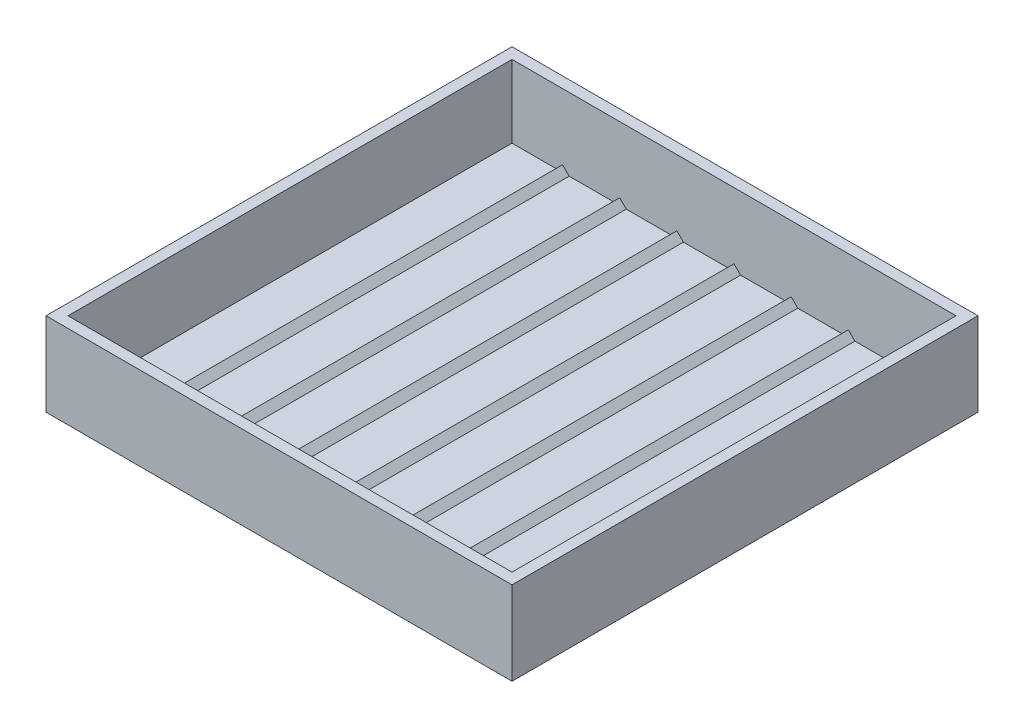
SolidWorks part; units mm, degrees
ref_plane "Front Plane" through (0, 0, 0) normal (0, 0, 1) x (1, 0, 0)
ref_plane "Top Plane" through (0, 0, 0) normal (0, 1, 0) x (1, 0, 0)
ref_plane "Right Plane" through (0, 0, 0) normal (1, 0, 0) x (0, 0, -1)
sketch "Sketch1" plane through (0, 0, 0) normal (0, 0, 1) x (1, 0, 0)
  line L0 (-50.5, -7) -> (-40.5, -7)
  line L1 (53, -9.5) -> (-53, -9.5)
  line L2 (53, -9.5) -> (53, 9.5)
  line L3 (53, 9.5) -> (-53, 9.5)
  line L4 (-53, -9.5) -> (-53, 9.5)
  line L5 (-24.5, -7) -> (-26, -5.5)
  line L6 (-50.5, -7) -> (-50.5, 9.5)
  line L7 (-37.5, -7) -> (-27.5, -7)
  line L8 (50.5, -7) -> (50.5, 9.5)
  line L10 (-24.5, -7) -> (-14.5, -7)
  line L12 (-11.5, -7) -> (-1.5, -7)
  line L14 (1.5, -7) -> (11.5, -7)
  line L16 (14.5, -7) -> (24.5, -7)
  line L18 (27.5, -7) -> (37.5, -7)
  line L20 (40.5, -7) -> (50.5, -7)
  line L21 (-26, -5.5) -> (-27.5, -7)
  line L22 (-37.5, -7) -> (-39, -5.5)
  line L23 (-39, -5.5) -> (-40.5, -7)
  line L24 (-11.5, -7) -> (-13, -5.5)
  line L25 (-13, -5.5) -> (-14.5, -7)
  line L26 (1.5, -7) -> (0, -5.5)
  line L27 (0, -5.5) -> (-1.5, -7)
  line L28 (14.5, -7) -> (13, -5.5)
  line L29 (13, -5.5) -> (11.5, -7)
  line L30 (27.5, -7) -> (26, -5.5)
  line L31 (26, -5.5) -> (24.5, -7)
  line L32 (40.5, -7) -> (39, -5.5)
  line L33 (39, -5.5) -> (37.5, -7)
  point P5 (0, 0)
extrude "Boss-Extrude1" add sketch "Sketch1" against normal blind 2.5 contours L33 L32 L20 L8 L3 L6 L0 L23 L22 L7 L21 L5 L10 L25 L24 L12 L27 L26 L14 L29 L28 L16 L31 L30 L18 | L32 L33 L18 L30 L31 L16 L28 L29 L14 L26 L27 L12 L24 L25 L10 L5 L21 L7 L22 L23 L0 L6 L3 L4 L1 L2 L8 L20 region at (0, 1.3239, 0) region at (0, -6.0165, 0)
extrude "Boss-Extrude2" add sketch "Sketch1<3>" along normal blind 50.5 contours L32 L33 L18 L30 L31 L16 L28 L29 L14 L26 L27 L12 L24 L25 L10 L5 L21 L7 L22 L23 L0 L6 L3 L4 L1 L2 L8 L20 region at (0, -6.0165, 0)
sketch "Sketch1<3>" plane through (0, 0, 0) normal (0, 0, 1) x (1, 0, 0) same geometry as "Sketch1"
mirror "Mirror4" about plane through (0, 0, 50.5) normal (0, 0, 1) of bodies 102
